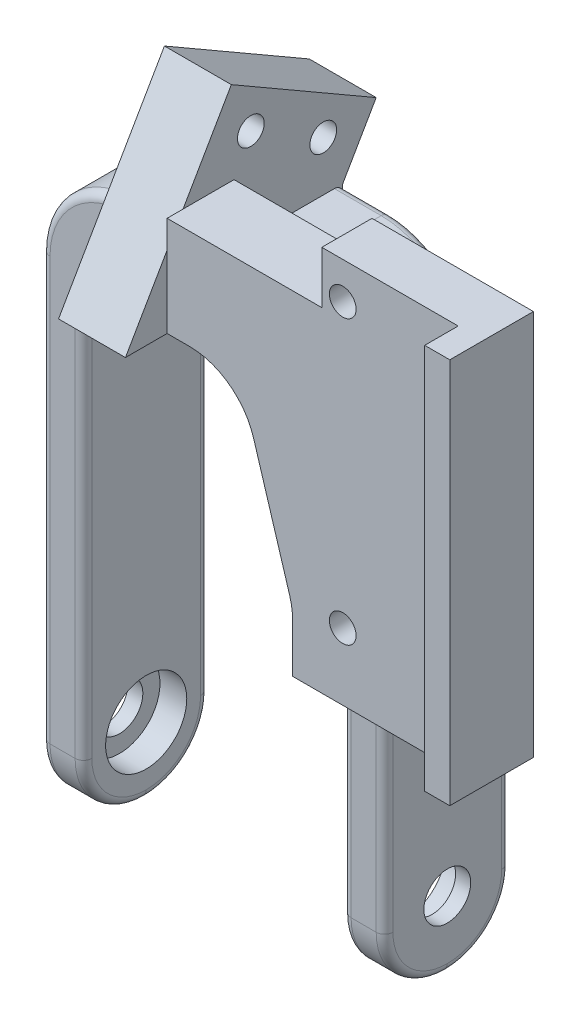
SolidWorks part; units mm, degrees
ref_plane "前视基准面" through (0, 0, 0) normal (0, 0, 1) x (1, 0, 0)
ref_plane "上视基准面" through (0, 0, 0) normal (0, 1, 0) x (1, 0, 0)
ref_plane "右视基准面" through (0, 0, 0) normal (1, 0, 0) x (0, 0, -1)
sketch "草图1" plane through (0, 0, 0) normal (0, 1, 0) x (1, 0, 0)
  line L1 (24, 7.5) -> (-17, 7.5)
  line L2 (24, 7.5) -> (24, -7.5)
  line L3 (24, -7.5) -> (-17, -7.5)
  line L4 (-17, 7.5) -> (-17, -7.5)
  line L5 (24, 7.5) -> (-17, -7.5) construction
  line L6 (24, -7.5) -> (-17, 7.5) construction
  point P0 (0, 0)
extrude "凸台-拉伸1" add sketch "草图1" against normal blind 68
sketch "草图3" plane through (0, 0, 7.5) normal (0, 0, 1) x (1, 0, 0)
  line L0 (-17, -68) -> (24, -68) construction
  line L1 (-12, -68) -> (19, -68)
  line L2 (-12, -68) -> (-12, -5)
  line L3 (-12, -5) -> (12.6087, -5)
  line L4 (19, -68) -> (19, -25.9143)
  line L5 (12.6087, -5) -> (19, -25.9143)
  line L6 (17, 0) -> (27.4891, -34.3238)
  line L7 (17, 0) -> (27.4891, 0)
  line L8 (27.4891, 0) -> (27.4891, -34.3238)
  line L9 (-17, 0) -> (24, 0) construction
  line L10 (-17, 0) -> (24, 0) construction
extrude "切除-拉伸1" cut sketch "草图3" against normal through all
fillet "圆角1" radius 8 3 edges at (-12, -5, 0) (19, -25.9143, 0) (12.6087, -5, 0)
fillet "圆角3" radius 7.5 4 edges at (21.5, -68, -7.5) (21.5, -68, 7.5) (-14.5, -68, -7.5) (-14.5, -68, 7.5)
sketch "草图4" plane through (24, 0, 0) normal (1, 0, 0) x (0, 0, -1)
  circle A0 centre (0, -60) radius 2.8
extrude "切除-拉伸2" cut sketch "草图4" against normal through all
sketch "草图6" plane through (19, 0, 0) normal (1, 0, 0) x (0, 0, -1)
  circle A0 centre (0, -60) radius 4.85
extrude "切除-拉伸4" cut sketch "草图6" along normal blind 3.2
ref_plane "基准面1" through (3.5, 0, 0) normal (1, 0, 0) x (0, 0, -1)
mirror "镜向2" about plane through (3.5, 0, 0) normal (1, 0, 0) of "切除-拉伸4"
sketch "草图7" plane through (0, 0, 0) normal (1, 0, 0) x (0, 0, -1)
  line L0 (-7.8205, 13.4641) -> (9.5, 3.4641) construction
  line L2 (-9.8205, 10) -> (-5.8205, 16.9282)
  line L3 (-5.8205, 16.9282) -> (11.5, 6.9282)
  line L4 (7.5, 0) -> (11.5, 6.9282)
  line L5 (7.5, 0) -> (7.5, -22.9063) construction
  line L6 (7.5, 0) -> (7.5, -22.9063) construction
  line L7 (-9.8205, 10) -> (-15.5907, 0.0057)
  line L8 (-7.5, 0) -> (7.5, 0)
  line L9 (-7.5, -5) -> (7.5, -5) construction
  line L10 (-7.5, -5) -> (7.5, -5) construction
  line L11 (-18.4808, -5) -> (-7.5, -5)
  line L12 (-7.5, -5) -> (-7.5, 0)
  line L13 (-18.4808, -5) -> (-15.5907, 0.0057)
  circle A2 centre (5.1699, 5.9641) radius 1.6
  circle A3 centre (-3.4904, 10.9641) radius 1.6
  dimension "D1" = 10
  dimension "D2" = 3.2
  dimension "D3" = 3.2
  dimension "D4" = 5
  dimension "D5" = 20
  dimension "D6" = 4
extrude "凸台-拉伸2" add sketch "草图7" along normal mid plane 8
fillet "圆角4" radius 10 2 edges at (17, 0, 0) (-17, 0, 0)
fillet "圆角2" radius 1 36 edges at (-17, -35.25, -7.5) (24, -41.7031, -7.5) (24, -41.7031, 7.5) (-17, -35.25, 7.5) (-9.6569, -7.3431, 7.5) (5.3441, -5, 7.5) (19, -43.8047, 7.5) (19, -43.8047, -7.5) (1.3441, -5, -7.5) (-9.6569, -7.3431, -7.5) (-12, -36.75, -7.5) (-12, -36.75, 7.5) (19, -65.8033, 5.3033) (19, -65.8033, -5.3033) (-12, -65.8033, -5.3033) (-12, -65.8033, 5.3033) (-17, -65.8033, 5.3033) (-17, -65.8033, -5.3033) (24, -65.8033, -5.3033) (24, -65.8033, 5.3033) (11.4473, -6.5694, 7.5) (16.4949, -17.7167, 7.5) (18.9122, -25.9274, 7.5) (18.9122, -25.9274, -7.5) (16.4949, -17.7167, -7.5) (11.4473, -6.5694, -7.5) (21.5814, -14.9919, -7.5) (21.5814, -14.9919, 7.5) (6.7997, 0, -7.5) (15.5481, -1.9618, -7.5) (6.7997, 0, 7.5) (15.5481, -1.9618, 7.5) (-5.5, 0, -7.5) (-14.0711, -2.9289, -7.5) (-5.5, 0, 7.5) (-14.0711, -2.9289, 7.5)
sketch "草图9" plane through (0, 5.6282, 7.5) normal (0, 0, 1) x (1, 0, 0)
  line L3 (38.8, -38.6282) -> (38.8, 7.546)
  line L4 (38.8, 7.546) -> (22.5, 7.546)
  line L5 (22.5, 7.546) -> (22.5, -38.6282)
  line L6 (22.5, -38.6282) -> (38.8, -38.6282)
  circle A0 centre (25, 3.1718) radius 1.6
  circle A1 centre (25, -30.6282) radius 1.6
  point P6 (0, 0)
  point P11 (12.4113, 29.9189)
  point P12 (22.5363, 29.7839)
  point P14 (21.7263, 29.6489)
  dimension "D1" = 3.2
  dimension "D2" = 3.2
  dimension "D3" = 33.8
  dimension "D4" = 25
  dimension "D5" = 13.8
  dimension "D6" = 2.5
  dimension "D7" = 25
  dimension "D8" = 8
extrude "凸台-拉伸3" add sketch "草图9" along normal blind 6 separate body
sketch "草图10" plane through (0, 0, 7.5) normal (0, 0, 1) x (1, 0, 0)
  line L2 (4, 6.9282) -> (4, -5)
  line L3 (19, -60.5) -> (19, -27.1094) construction
  line L4 (18.6507, -24.7714) -> (14.339, -10.662) construction
  line L5 (6.6883, -5) -> (4, -5) construction
  line L6 (19, -33) -> (19, -27.1094)
  line L7 (18.6507, -24.7714) -> (14.339, -10.662)
  line L8 (6.6883, -5) -> (4, -5)
  line L9 (22.5, 6.9282) -> (22.5, -33)
  line L10 (22.5, -33) -> (38.8, -33) construction
  line L11 (22.5, 13.1742) -> (22.5, -33) construction
  line L12 (22.5, -33) -> (19, -33)
  line L13 (4, 6.9282) -> (22.5, 6.9282)
  arc A0 (19, -27.1094) -> (18.6507, -24.7714) centre (11, -27.1094) ccw construction
  arc A1 (14.339, -10.662) -> (6.6883, -5) centre (6.6883, -13) ccw construction
  arc A2 (19, -27.1094) -> (18.6507, -24.7714) centre (11, -27.1094) ccw
  arc A3 (14.339, -10.662) -> (6.6883, -5) centre (6.6883, -13) ccw
extrude "凸台-拉伸5" add sketch "草图10" along normal up to surface (6 mm away) and the other way blind 2 up to face at (26.6, 8.8, 13.5)
sketch "草图11" plane through (0, 0, 7.5) normal (0, 0, -1) x (-1, 0, 0)
  line L1 (-38.8, 13.1742) -> (-41.8, 13.1742)
  line L2 (-38.8, 13.1742) -> (-38.8, -33)
  line L3 (-38.8, -33) -> (-41.8, -33)
  line L4 (-41.8, 13.1742) -> (-41.8, -33)
  dimension "D1" = 3
extrude "凸台-拉伸6" add sketch "草图11" against normal blind 10
